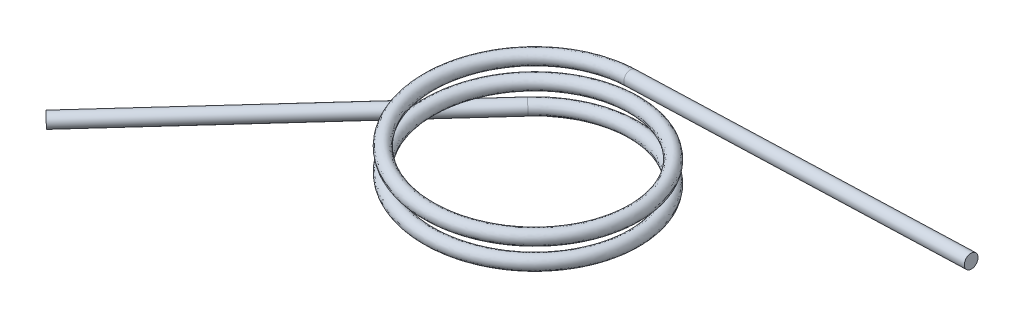
SolidWorks part; units mm, degrees
note: '?' marks a value the reader was unsure of.
ref_plane "Front Plane" through (0, 0, 0) normal (0, 0, 1) x (1, 0, 0)
ref_plane "Top Plane" through (0, 0, 0) normal (0, 1, 0) x (1, 0, 0)
ref_plane "Right Plane" through (0, 0, 0) normal (1, 0, 0) x (0, 0, -1)
sketch "Sketch2" plane through (0, 0, 0) normal (0, 1, 0) x (1, 0, 0)
  circle A0 centre (0, 0) radius 30.607
  dimension "D1" = 61.214
curve "Helix/Spiral1" pitch 6.477 height 13.7636 turns 2.125
sweep "Sweep1" add path "Helix/Spiral1" circular profile diameter 4.064 parameters "D3"=4.064
sketch "Sketch15" plane through (-0.3274, -0.0156, 0.3274) normal (-0.7067, -0.0337, 0.7067) x (-0.6869, -0.2066, -0.6968)
  circle A1 centre (32.7896, 7.1326) radius 2.032
  circle A2 centre (32.7896, 7.1326) radius 2.032
  dimension "D1" = 0
extrude "Boss-Extrude1" add sketch "Sketch15" along normal blind 101.6
sketch "Sketch24" plane through (0, 0, 0) normal (0.9994, 0.0337, 0) x (0.0061, -0.1818, -0.9833)
  circle A1 centre (30.0962, 5.5682) radius 2.032
  circle A2 centre (30.0962, 5.5682) radius 2.032
  dimension "D1" = 0
extrude "Boss-Extrude2" add sketch "Sketch24" along normal blind 101.6
ref_axis "Axis1" through (0, 50.5632, 0) along (0, -1, 0)?
